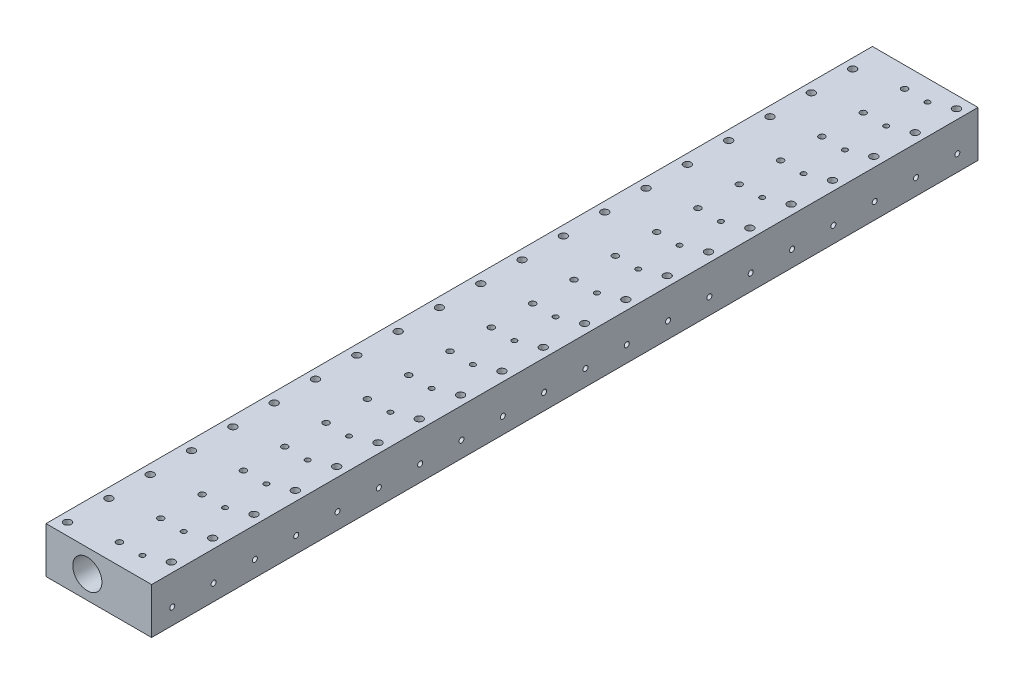
SolidWorks part; units mm, degrees
ref_plane "Front Plane" through (0, 0, 0) normal (0, 0, 1) x (1, 0, 0)
ref_plane "Top Plane" through (0, 0, 0) normal (0, 1, 0) x (1, 0, 0)
ref_plane "Right Plane" through (0, 0, 0) normal (1, 0, 0) x (0, 0, -1)
sketch "Sketch1" plane through (0, 0, 0) normal (0, 0, 1) x (1, 0, 0)
  line L1 (-11.5, -5) -> (11.5, -5)
  line L2 (-11.5, -5) -> (-11.5, 5)
  line L3 (-11.5, 5) -> (11.5, 5)
  line L4 (11.5, -5) -> (11.5, 5)
  line L5 (-11.5, -5) -> (11.5, 5) construction
  line L6 (-11.5, 5) -> (11.5, -5) construction
  point P0 (0, 0)
  dimension "D1" = 23
  dimension "D2" = 10
extrude "Boss-Extrude1" add sketch "Sketch1" against normal blind 180
hole_wizard "#55 (0.052) Diameter Hole1" positions "Sketch2" profile "Sketch4" hole size "#55" standard "ANSI Inch"
sketch "Sketch2" plane through (0, 5, 0) normal (0, 1, 0) x (1, 0, 0)
  line L0 (11.5, 0) -> (-11.5, 0) construction
  point P0 (0, 4.5)
  dimension "D1" = 4.5
sketch "Sketch4" plane through (0, 5, -4.5) normal (1, 0, 0) x (0, 0, 1)
  line L0 (0, 0) -> (0, 7.3968)
  line L1 (0, 7.3968) -> (0.6604, 7)
  line L2 (0.6604, 7) -> (0.6604, 0)
  line L5 (0.6604, 0) -> (0, 0)
  line L10 (0, 7.3968) -> (-0.6604, 7) construction
  line L11 (0, -6.35) -> (0, 107.95) construction
  dimension "Hole Dia." = 1.3208
  dimension "Hole Depth" = 7
  dimension "Drill Angle" = 118
sketch "Sketch5" plane through (0, 0, 0) normal (0, 0, 1) x (1, 0, 0)
  circle A0 centre (-2.5, 0) radius 3.175
  dimension "D2" = 6.35
  dimension "D1" = 2.5
extrude "Cut-Extrude1" cut sketch "Sketch5" against normal through all
hole_wizard "M2x0.4 Tapped Hole1" positions "Sketch6" profile "Sketch8" tap size "M2x0.4" standard "ANSI Metric"
sketch "Sketch6" plane through (0, 5, 0) normal (0, 1, 0) x (1, 0, 0)
  line L0 (0, 4.5) -> (5, 4.5) construction
  point P0 (9.4, 6.4)
  point P2 (-9.4, 2.6)
  dimension "D1" = 9.4
  dimension "D2" = 9.4
  dimension "D3" = 1.9
  dimension "D4" = 1.9
sketch "Sketch8" plane through (9.4, 5, -6.4) normal (1, 0, 0) x (0, 0, 1)
  line L0 (0, 0) -> (0, 5.6807)
  line L1 (0, 5.6807) -> (0.8, 5.2)
  line L2 (0.8, 5.2) -> (0.8, 0)
  line L5 (0.8, 0) -> (0, 0)
  line L10 (0, 5.6807) -> (-0.8, 5.2) construction
  line L11 (0, -6.35) -> (0, 107.95) construction
  dimension "Tap Drill Dia." = 1.6
  dimension "Tap Drill Depth" = 5.2
  dimension "Drill Angle" = 118
cosmetic thread "Hole Thread1" parameters "D1"=4, "D2"=2
cosmetic thread "Hole Thread2" parameters "D1"=4, "D2"=2
hole_wizard "#57 (0.043) Diameter Hole1" positions "Sketch11" profile "Sketch12" hole size "#57" standard "ANSI Inch"
sketch "Sketch11" plane through (11.5, 0, 0) normal (1, 0, 0) x (0, 0, -1)
  line L0 (0, -5) -> (0, 5) construction
  line L1 (180, 5) -> (0, 5) construction
  point P0 (4.5, -1.5)
  dimension "D1" = 4.5
  dimension "D2" = 6.5
sketch "Sketch12" plane through (11.5, -1.5, -4.5) normal (0, 1, 0) x (0, 0, -1)
  line L0 (0, 0) -> (0, 6.3281)
  line L1 (0, 6.3281) -> (0.5461, 6)
  line L2 (0.5461, 6) -> (0.5461, 0)
  line L5 (0.5461, 0) -> (0, 0)
  line L10 (0, 6.3281) -> (-0.5461, 6) construction
  line L11 (0, -6.35) -> (0, 107.95) construction
  dimension "Hole Dia." = 1.0922
  dimension "Hole Depth" = 6
  dimension "Drill Angle" = 118
hole_wizard "#57 (0.043) Diameter Hole2" positions "Sketch13" profile "Sketch14" hole size "#57" standard "ANSI Inch"
sketch "Sketch13" plane through (0, 5, 0) normal (0, 1, 0) x (1, 0, 0)
  line L0 (0, 4.5) -> (5, 4.5)
  point P0 (5, 4.5)
  dimension "D1" = 5
sketch "Sketch14" plane through (5, 5, -4.5) normal (1, 0, 0) x (0, 0, 1)
  line L0 (0, 0) -> (0, 7.8281)
  line L1 (0, 7.8281) -> (0.5461, 7.5)
  line L2 (0.5461, 7.5) -> (0.5461, 0)
  line L5 (0.5461, 0) -> (0, 0)
  line L10 (0, 7.8281) -> (-0.5461, 7.5) construction
  line L11 (0, -6.35) -> (0, 107.95) construction
  dimension "Hole Dia." = 1.0922
  dimension "Hole Depth" = 7.5
  dimension "Drill Angle" = 118
pattern_linear "LPattern1" count 20 spacing 9 along (0, 0, -1) of "#55 (0.052) Diameter Hole1", "M2x0.4 Tapped Hole1", "#57 (0.043) Diameter Hole1", "#57 (0.043) Diameter Hole2"
